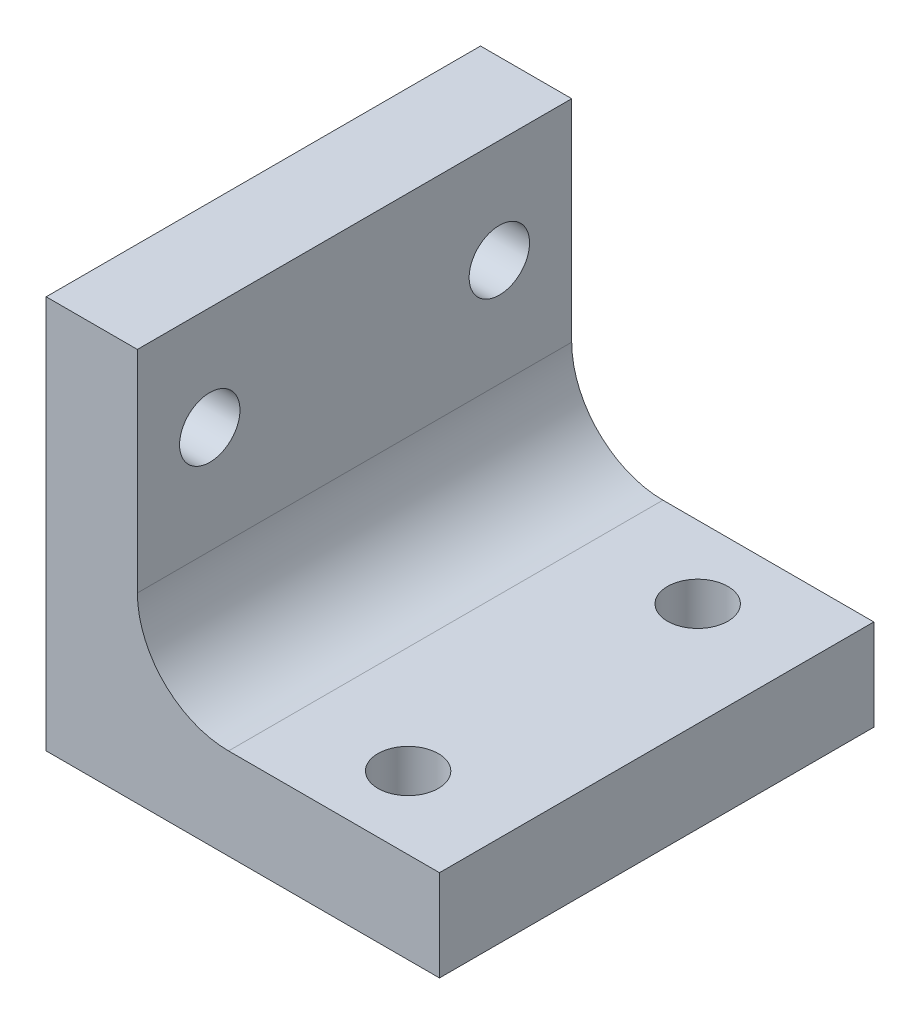
SolidWorks part; units mm, degrees
material "AISI 1045 Steel, cold drawn"
ref_plane "Front Plane" through (0, 0, 0) normal (0, 0, 1) x (1, 0, 0)
ref_plane "Top Plane" through (0, 0, 0) normal (0, 1, 0) x (1, 0, 0)
ref_plane "Right Plane" through (0, 0, 0) normal (1, 0, 0) x (0, 0, -1)
sketch "Sketch1" plane through (0, 0, 0) normal (0, 0, 1) x (1, 0, 0)
  line L0 (0, 0) -> (34.5, 0)
  line L1 (34.5, 0) -> (34.5, 8)
  line L2 (34.5, 8) -> (8, 8)
  line L3 (8, 8) -> (8, 34.5) construction
  line L4 (8, 34.5) -> (0, 34.5) construction
  line L5 (0, 34.5) -> (0, 0) construction
  line L6 (0, 0) -> (8, 8)
  dimension "D1" = 34.5
  dimension "D2" = 8
extrude "Boss-Extrude1" add sketch "Sketch1" along normal mid plane 38.1
hole_wizard "M5 Clearance Hole1" positions "Sketch2" profile "Sketch3" hole size "M5" standard "ANSI Metric" end condition up to next
sketch "Sketch2" plane through (0, 8, 0) normal (0, 1, 0) x (1, 0, 0)
  line L0 (25.4, 12.7) -> (25.4, -12.7) construction
  line L2 (0, 0) -> (25.4, 0) construction
  point P1 (25.4, 12.7)
  point P2 (25.4, -12.7)
  dimension "D1" = 25.4
  dimension "D2" = 25.4
sketch "Sketch3" plane through (25.4, 8, -12.7) normal (1, 0, 0) x (0, 0, 1)
  line L0 (0, 0) -> (0, 8)
  line L1 (0, 8) -> (2.65, 8)
  line L2 (2.65, 8) -> (2.65, 0)
  line L5 (2.65, 0) -> (0, 0)
  line L11 (0, -6.35) -> (0, 107.95) construction
  dimension "Thru Hole Dia." = 5.3
  dimension "Thru Hole Depth" = 8
mirror "Mirror1" about plane through (0, 0, 19.05) normal (0.7071, -0.7071, 0) of bodies 102
fillet "Fillet1" radius 8 1 edges at (8, 8, 0)
